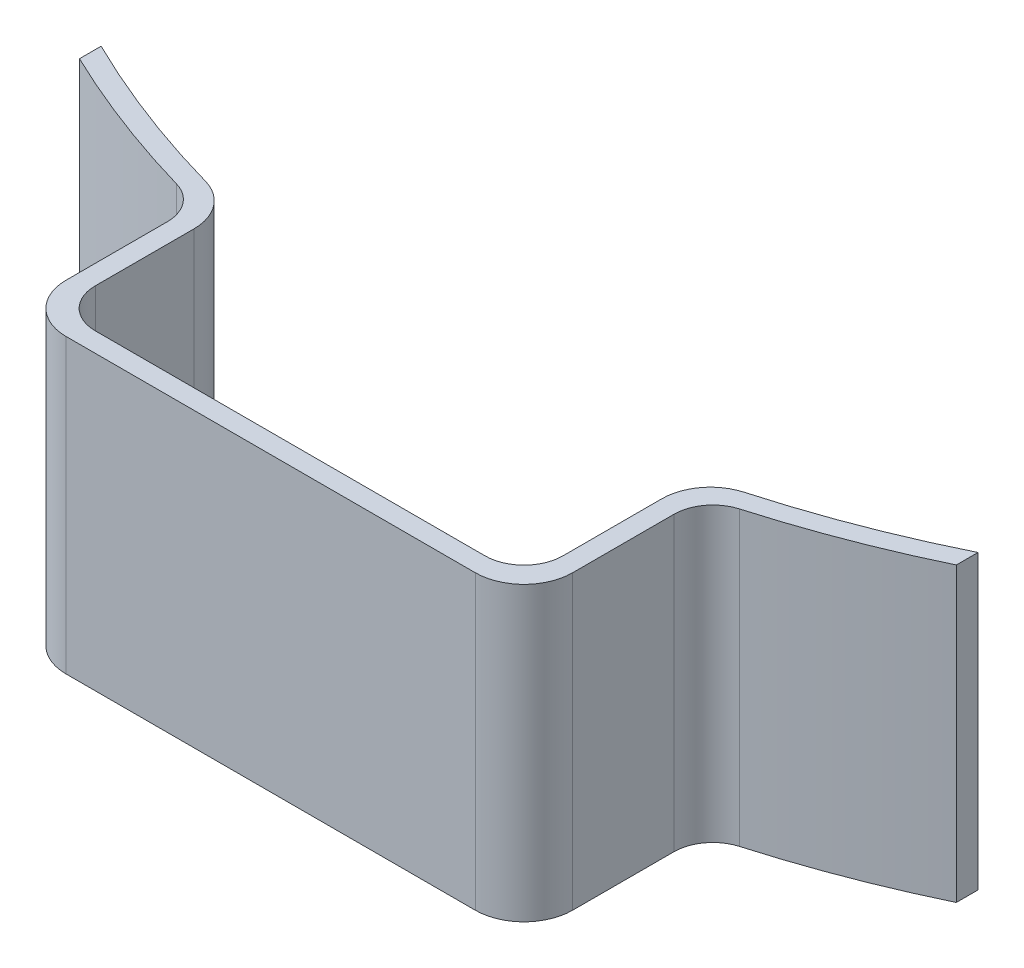
SolidWorks part; units mm, degrees
ref_plane "Спереди" through (0, 0, 0) normal (0, 0, 1) x (1, 0, 0)
ref_plane "Сверху" through (0, 0, 0) normal (0, 1, 0) x (1, 0, 0)
ref_plane "Справа" through (0, 0, 0) normal (1, 0, 0) x (0, 0, -1)
sketch "Эскиз1" plane through (0, 0, 0) normal (0, 1, 0) x (1, 0, 0)
  line L0 (0, -1000) -> (0, 49000) construction
  line L1 (-22.5, -46.8802) -> (-22.5, -45.7684)
  line L2 (22.5, -46.8802) -> (22.5, -45.7684)
  line L3 (12, -58.5681) -> (12, -49.5681)
  line L4 (-12, -58.5681) -> (-12, -49.5681)
  line L5 (-12, -58.5681) -> (12, -58.5681)
  line L6 (-13, -50.3488) -> (-13, -59.5681)
  line L7 (-13, -59.5681) -> (13, -59.5681)
  line L8 (13, -50.3488) -> (13, -59.5681)
  circle A0 centre (0, 0) radius 51 construction
  arc A1 (-22.5, -45.7684) -> (-12, -49.5681) centre (0, 0) ccw
  arc A2 (0, 51) -> (-22.5, -45.7684) centre (0, 0) ccw construction
  arc A3 (22.5, -45.7684) -> (0, 51) centre (0, 0) ccw construction
  arc A4 (-12, -49.5681) -> (0, -51) centre (0, 0) ccw construction
  arc A5 (12, -49.5681) -> (22.5, -45.7684) centre (0, 0) ccw
  arc A6 (0, -51) -> (12, -49.5681) centre (0, 0) ccw construction
  arc A7 (-22.5, -46.8802) -> (-13, -50.3488) centre (0, 0) ccw
  arc A8 (22.5, -46.8802) -> (13, -50.3488) centre (0, 0) cw
  point P16 (0, -62.7151)
  point P18 (12, -56.9922)
  point P20 (0, -59.5681)
  dimension "D3" = 1
  dimension "D1" = 45
  dimension "D2" = 24
  dimension "D4" = 1
  dimension "D5" = 1
  dimension "D6" = 10
extrude "Бобышка-Вытянуть1" add sketch "Эскиз1" along normal up to surface (15 mm away)
fillet "Скругление1" radius 2 4 edges at (12, 7.5, 58.5681) (-12, 7.5, 58.5681) (13, 7.5, 50.3488) (-13, 7.5, 50.3488)
fillet "Скругление2" radius 2.5 4 edges at (13, 7.5, 59.5681) (-13, 7.5, 59.5681) (12, 7.5, 49.5681) (-12, 7.5, 49.5681)
